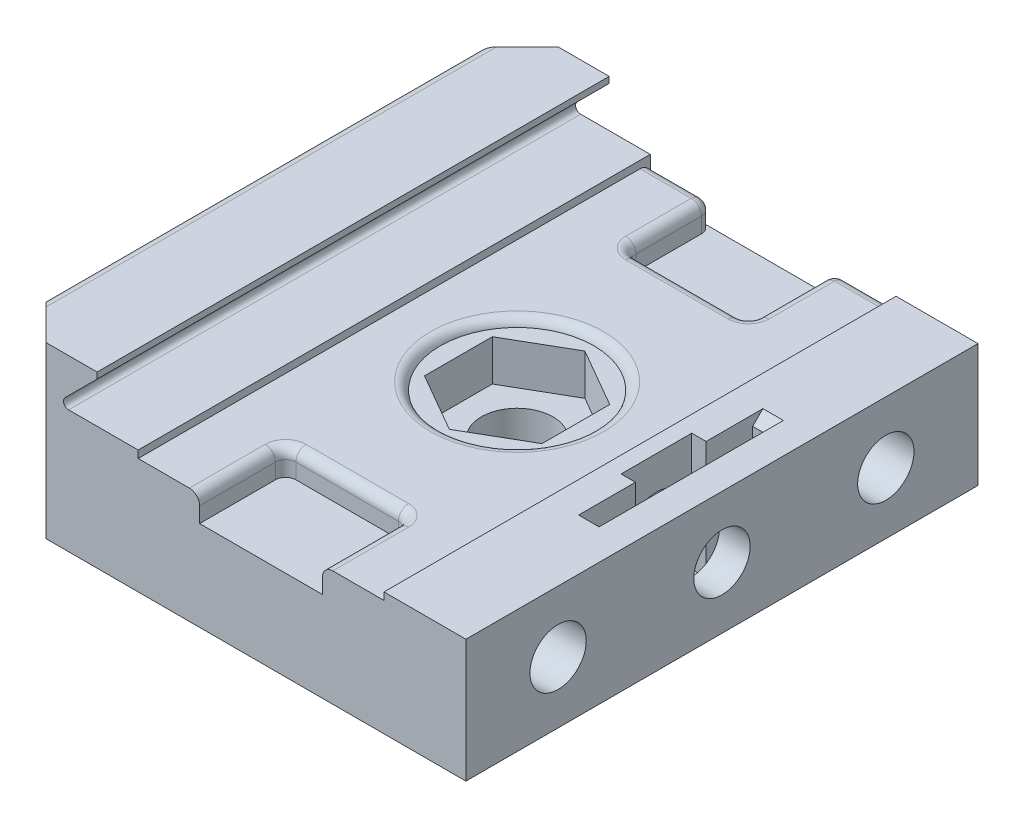
SolidWorks part; units mm, degrees
ref_plane "Front Plane" through (0, 0, 0) normal (0, 0, 1) x (1, 0, 0)
ref_plane "Top Plane" through (0, 0, 0) normal (0, 1, 0) x (1, 0, 0)
ref_plane "Right Plane" through (0, 0, 0) normal (1, 0, 0) x (0, 0, -1)
sketch "Sketch1" plane through (0, 0, 0) normal (0, 1, 0) x (1, 0, 0)
  line L1 (22.5, -25) -> (-22.5, -25)
  line L2 (22.5, -25) -> (22.5, 25)
  line L3 (22.5, 25) -> (-22.5, 25)
  line L4 (-22.5, -25) -> (-22.5, 25)
  line L5 (22.5, -25) -> (-22.5, 25) construction
  line L6 (22.5, 25) -> (-22.5, -25) construction
  point P0 (0, 0)
  dimension "D1" = 45
  dimension "D2" = 50
extrude "Boss-Extrude1" add sketch "Sketch1" along normal blind 16
sketch "Sketch3" plane through (0, 0, 25) normal (0, 0, 1) x (1, 0, 0)
  line L0 (-13.5, 16) -> (-17.5, 12)
  line L1 (22.5, 16) -> (-13.5, 16)
  line L2 (22.5, 16) -> (22.5, 12)
  line L3 (22.5, 12) -> (-17.5, 12)
  dimension "D1" = 40
  dimension "D2" = 36
  dimension "D3" = 45
extrude "Cut-Extrude1" cut sketch "Sketch3" against normal through all
sketch "Sketch4" plane through (0, 12, 0) normal (0, 1, 0) x (1, 0, 0)
  line L0 (22.5, 25) -> (-17.5, -25) construction
  line L1 (-17.5, -25) -> (22.5, -25)
  line L2 (-17.5, -25) -> (-17.5, 25)
  line L3 (-17.5, 25) -> (22.5, 25)
  line L4 (22.5, -25) -> (22.5, 25)
  line L5 (22.5, -25) -> (-17.5, 25) construction
  line L7 (-9.5, -25) -> (14.5, -25)
  line L8 (-9.5, -25) -> (-9.5, 25)
  line L9 (-9.5, 25) -> (14.5, 25)
  line L10 (14.5, -25) -> (14.5, 25)
  line L11 (-9.5, -25) -> (14.5, 25) construction
  line L12 (-9.5, 25) -> (14.5, -25) construction
  point P6 (2.5, 0)
  dimension "D1" = 24
extrude "Cut-Extrude2" cut sketch "Sketch4" against normal blind 0.72 contours L8 L9 L10 L7
sketch "Sketch5" plane through (0, 0, 25) normal (0, 0, 1) x (1, 0, 0)
  line L0 (-22.5, 16) -> (-13.5, 16)
  line L1 (-13.5, 16) -> (-13.51, 15.99)
  line L2 (-13.5, 16) -> (-17.5, 12) construction
  line L3 (-13.51, 15.99) -> (-22.5, 15.99)
  line L4 (-22.5, 16) -> (-22.5, 0) construction
  line L5 (-22.5, 15.99) -> (-22.5, 16)
  dimension "D1" = 0.01
extrude "Cut-Extrude3" cut sketch "Sketch5" against normal through all
sketch "Sketch8" plane through (0, 11.28, 0) normal (0, 1, 0) x (1, 0, 0)
  line L0 (-9.5, -25) -> (-9.5, 25) construction
  line L1 (-9.5, -25) -> (14.5, -25) construction
  circle A0 centre (2.5, 0) radius 7.5
  dimension "D1" = 12
  dimension "D2" = 25
extrude "Cut-Extrude4" cut sketch "Sketch8" against normal blind 0.72
hole_wizard "M6 Clearance Hole2" positions "Sketch9" profile "Sketch10" hole size "M6" standard "ANSI Metric" end condition through all
sketch "Sketch9" plane through (0, 10.56, 0) normal (0, 1, 0) x (1, 0, 0)
  point P0 (2.5, 0)
sketch "Sketch10" plane through (2.5, 10.56, 0) normal (1, 0, 0) x (0, 0, 1)
  line L0 (0, 0) -> (0, 10.56)
  line L1 (0, 10.56) -> (3.5, 10.56)
  line L2 (3.5, 10.56) -> (3.5, 0)
  line L5 (3.5, 0) -> (0, 0)
  line L11 (0, -6.35) -> (0, 107.95) construction
  dimension "Thru Hole Dia." = 7
  dimension "Thru Hole Depth" = 10.56
sketch "Sketch12" plane through (0, 11.28, 0) normal (0, 1, 0) x (1, 0, 0)
  line L0 (-9.5, 25) -> (14.5, 25) construction
  line L1 (7.5, 16.6) -> (-2.5, 16.6)
  line L2 (8.5, 17.6) -> (8.5, 25)
  line L4 (-3.5, 17.6) -> (-3.5, 25)
  line L5 (-3.5, 21.3) -> (8.5, 21.3) construction
  line L6 (2.5, 25) -> (2.5, 16.6) construction
  line L7 (-3.5, 25) -> (8.5, 25)
  line L8 (-9.5, -25) -> (-9.5, 25) construction
  arc A0 (7.5, 16.6) -> (8.5, 17.6) centre (7.5, 17.6) ccw
  arc A1 (-2.5, 16.6) -> (-3.5, 17.6) centre (-2.5, 17.6) cw
  point P0 (2.5, 25)
  point P9 (8.5, 16.6)
  point P12 (-3.5, 16.6)
  point P17 (2.5, 21.3)
  dimension "D2" = 1
  dimension "D1" = 12
  dimension "D3" = 12
  dimension "D4" = 0
  dimension "D5" = 7.4
extrude "Cut-Extrude5" cut sketch "Sketch12" against normal blind 2.5
fillet "Fillet1" radius 1 2 edges at (8.5, 10.03, -25) (-3.5, 10.03, -25)
mirror "Mirror2" about plane through (0, 0, 0) normal (0, 0, 1) of "Cut-Extrude5"
fillet "Fillet2" radius 1 15 edges at (-7, 11.28, -25) (-3.7929, 11.28, -24.7071) (12, 11.28, -25) (8.7929, 11.28, -24.7071) (8.5, 11.28, -20.8) (8.2071, 11.28, -16.8929) (2.5, 11.28, -16.6) (-3.2071, 11.28, -16.8929) (-3.5, 11.28, 21.3) (-3.2071, 11.28, 16.8929) (8.5, 11.28, 21.3) (8.2071, 11.28, 16.8929) (-5, 11.28, 0) (-3.5, 11.28, -20.8) (2.5, 11.28, 16.6)
fillet "Fillet4" radius 0.5 1 edges at (-17.5, 12, 0)
sketch "Sketch14" plane through (0, 12, 0) normal (0, 1, 0) x (1, 0, 0)
  line L0 (14.5, 25) -> (22.5, 25) construction
  line L1 (19.5, -8) -> (17.5, -8)
  line L2 (19.5, -8) -> (19.5, 8)
  line L3 (19.5, 8) -> (17.5, 8)
  line L4 (17.5, -8) -> (17.5, -3.45)
  line L5 (19.5, -8) -> (17.5, 8) construction
  line L6 (19.5, 8) -> (17.5, -8) construction
  line L7 (17.5, 3.45) -> (16.1, 3.45)
  line L8 (17.5, -3.45) -> (16.1, -3.45)
  line L11 (16.1, -3.45) -> (16.1, 3.45)
  line L12 (19.5, -1.4375) -> (16.1, 3.45) construction
  line L13 (19.5, 1.4375) -> (16.1, -3.45) construction
  line L14 (17.5, 3.45) -> (17.5, 8)
  point P0 (18.5, 0)
  point P7 (18.5, 0)
  dimension "D1" = 16
  dimension "D2" = 25
  dimension "D3" = 2
  dimension "D4" = 6.9
  dimension "D5" = 1.4
  dimension "D6" = 4.55
extrude "Cut-Extrude7" cut sketch "Sketch14" against normal blind 11.5
sketch "Sketch18" plane through (22.5, 0, 0) normal (1, 0, 0) x (0, 0, -1)
  circle A0 centre (0, 6) radius 2.75
  dimension "D1" = 5.5
extrude "Cut-Extrude8" cut sketch "Sketch18" against normal blind 14.5
sketch "Sketch19" plane through (22.5, 0, 0) normal (1, 0, 0) x (0, 0, -1)
  line L0 (-25, 12) -> (-25, 0) construction
  line L1 (25, 12) -> (25, 0) construction
  circle A0 centre (-16, 6) radius 2.75
  circle A1 centre (16, 6) radius 2.75
  dimension "D3" = 5.5
  dimension "D4" = 5.5
  dimension "D1" = 9
  dimension "D2" = 9
extrude "Cut-Extrude9" cut sketch "Sketch19" against normal blind 10
sketch "Sketch20" plane through (0, 0, 0) normal (0, -1, 0) x (-1, 0, 0)
  line L1 (-4.65, 8.25) -> (-0.35, 8.25)
  line L2 (-4.65, 8.25) -> (-4.65, -8.25)
  line L3 (-4.65, -8.25) -> (-0.35, -8.25)
  line L4 (-0.35, 8.25) -> (-0.35, -8.25)
  line L5 (-4.65, 8.25) -> (-0.35, -8.25) construction
  line L6 (-4.65, -8.25) -> (-0.35, 8.25) construction
  dimension "D1" = 4.3
  dimension "D2" = 16.5
extrude "Cut-Extrude10" [suppressed] cut sketch "Sketch20" against normal blind 2
sketch "Sketch21" plane through (0, 15.99, 0) normal (0, 1, 0) x (1, 0, 0)
  line L1 (-22.5, 25) -> (-13.51, 25)
  line L2 (-22.5, 25) -> (-22.5, -25)
  line L3 (-22.5, -25) -> (-13.51, -25)
  line L4 (-13.51, 25) -> (-13.51, -25)
extrude "Boss-Extrude2" add sketch "Sketch21" along normal blind 0.6
chamfer "Chamfer1" distance 4 angle 45 2 edges at (-22.5, 8.295, -25) (-22.5, 8.295, 25)
fillet "Fillet5" radius 1 1 edges at (-22.5, 16.59, 0)
sketch "Sketch23" plane through (0, 10.56, 0) normal (0, 1, 0) x (1, 0, 0)
  line L1 (2.5, 6.6188) -> (-3.2321, 3.3094)
  line L2 (-3.2321, 3.3094) -> (-3.2321, -3.3094)
  line L3 (-3.2321, -3.3094) -> (2.5, -6.6188)
  line L4 (2.5, -6.6188) -> (8.2321, -3.3094)
  line L5 (8.2321, -3.3094) -> (8.2321, 3.3094)
  line L6 (8.2321, 3.3094) -> (2.5, 6.6188)
  circle A0 centre (2.5, 0) radius 5.7321 construction
extrude "Cut-Extrude11" cut sketch "Sketch23" against normal blind 4
chamfer "Chamfer2" distance 1 angle 45 2 edges at (18.5, 12, 8) (18.5, 12, -8)
